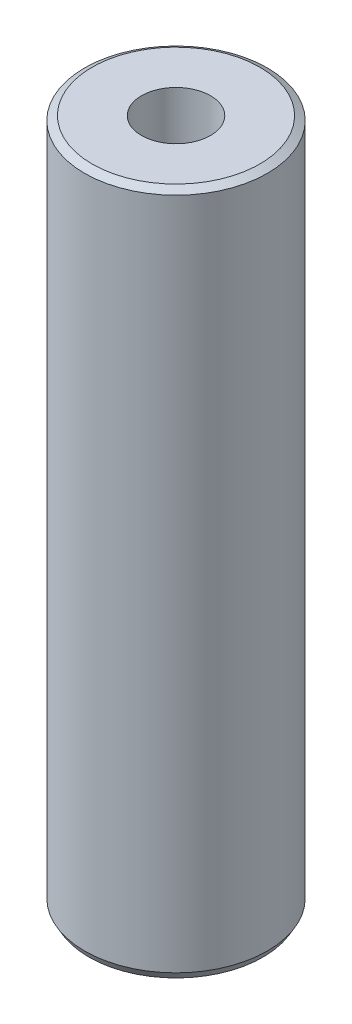
SolidWorks part; units mm, degrees
ref_plane "Front Plane" through (0, 0, 0) normal (0, 0, 1) x (1, 0, 0)
ref_plane "Top Plane" through (0, 0, 0) normal (0, 1, 0) x (1, 0, 0)
ref_plane "Right Plane" through (0, 0, 0) normal (1, 0, 0) x (0, 0, -1)
sketch "Sketch1" plane through (0, 0, 0) normal (0, 1, 0) x (1, 0, 0)
  circle A0 centre (0, 0) radius 60
  dimension "SHAFT_OD" = 120
extrude "Boss-Extrude1" add sketch "Sketch1" along normal blind 449.9709
sketch "Sketch2" plane through (0, 0, 0) normal (0, 1, 0) x (1, 0, 0)
  circle A0 centre (0, 0) radius 22.6558
  dimension "BORE_D" = 45.3117
extrude "Cut-Extrude1" cut sketch "Sketch2" along normal through all
chamfer "Chamfer1" distance 2.8449 angle 60 2 edges at (0, 449.9709, 60) (0, 0, 60) first distance on face at (0, 449.9709, 60) first distance on face at (0, 0, 22.6558)
